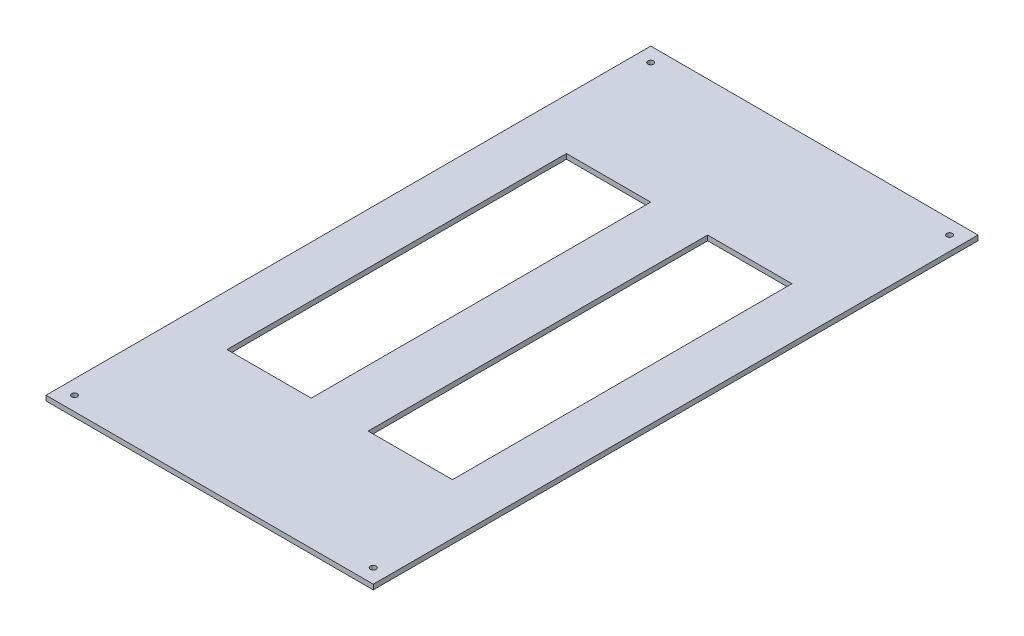
SolidWorks part; units mm, degrees
material "Acrylic (Medium-high impact)"
ref_plane "Front Plane" through (0, 0, 0) normal (0, 0, 1) x (1, 0, 0)
ref_plane "Top Plane" through (0, 0, 0) normal (0, 1, 0) x (1, 0, 0)
ref_plane "Right Plane" through (0, 0, 0) normal (1, 0, 0) x (0, 0, -1)
sketch "Sketch1" plane through (0, 0, 0) normal (0, 1, 0) x (1, 0, 0)
  line L0 (0, 212.5) -> (0, -212.5) construction
  line L1 (-115, 212.5) -> (115, 212.5)
  line L2 (-115, 212.5) -> (-115, -212.5)
  line L3 (-115, -212.5) -> (115, -212.5)
  line L4 (115, 212.5) -> (115, -212.5)
  line L5 (-115, 212.5) -> (115, -212.5) construction
  line L6 (-115, -212.5) -> (115, 212.5) construction
  line L8 (-115, 0) -> (115, 0) construction
  point P0 (0, 0)
  point P7 (105, -148.7228)
  point P8 (-105, 202.5)
  point P9 (0, 0)
  point P13 (0, 0)
  point P14 (105, 202.5)
  point P15 (0, 0)
  point P16 (105, -202.5)
  point P17 (-105, -202.5)
  point P18 (0, 0)
  dimension "D1" = 210
  dimension "D2" = 405
  dimension "D3" = 10
  dimension "D4" = 10
extrude "Boss-Extrude1" add sketch "Sketch1" against normal blind 3.5 contours L1 L4 L3 L2
hole_wizard "Ø4.0 (4) Diameter Hole1" positions "Sketch2" profile "Sketch4" hole size "Ø4.0" standard "ANSI Metric" end condition through all
sketch "Sketch2" plane through (0, 0, 0) normal (0, 1, 0) x (1, 0, 0)
  point P0 (-105, 202.5)
  point P3 (105, 202.5)
  point P6 (105, -202.5)
  point P9 (-105, -202.5)
sketch "Sketch4" plane through (-105, 0, -202.5) normal (1, 0, 0) x (0, 0, 1)
  line L0 (0, 0) -> (0, 3.5)
  line L1 (0, 3.5) -> (2, 3.5)
  line L2 (2, 3.5) -> (2, 0)
  line L5 (2, 0) -> (0, 0)
  line L11 (0, -6.35) -> (0, 107.95) construction
  dimension "Thru Hole Dia." = 4
  dimension "Thru Hole Depth" = 3.5
sketch "Sketch5" plane through (0, 0, 0) normal (0, 1, 0) x (1, 0, 0)
  line L0 (0, 212.5) -> (0, -212.5) construction
  line L1 (-74.2385, 112.5) -> (-25, 112.5) construction
  line L2 (-74.2385, 112.5) -> (-74.2385, -116.1) construction
  line L3 (-74.2385, -116.1) -> (-25, -116.1) construction
  line L4 (-25, 112.5) -> (-25, -116.1) construction
  line L5 (25, 112.5) -> (25, -116.1) construction
  line L6 (-79.2385, 117.5) -> (-20, 117.5)
  line L7 (-79.2385, 117.5) -> (-79.2385, -121.1)
  line L8 (-79.2385, -121.1) -> (-20, -121.1)
  line L9 (-20, 117.5) -> (-20, -121.1)
  line L10 (74.2385, -116.1) -> (25, -116.1) construction
  line L11 (74.2385, 112.5) -> (74.2385, -116.1) construction
  line L12 (74.2385, 112.5) -> (25, 112.5) construction
  line L13 (20, 117.5) -> (20, -121.1)
  line L14 (79.2385, -121.1) -> (20, -121.1)
  line L15 (79.2385, 117.5) -> (79.2385, -121.1)
  line L16 (79.2385, 117.5) -> (20, 117.5)
  dimension "D1" = 90
  dimension "D2" = 228.6
  dimension "D3" = 49.2385
  dimension "D4" = 5
  dimension "D5" = 5
  dimension "D6" = 5
  dimension "D7" = 5
  dimension "D8" = 25
extrude "Cut-Extrude1" cut sketch "Sketch5" against normal through all
